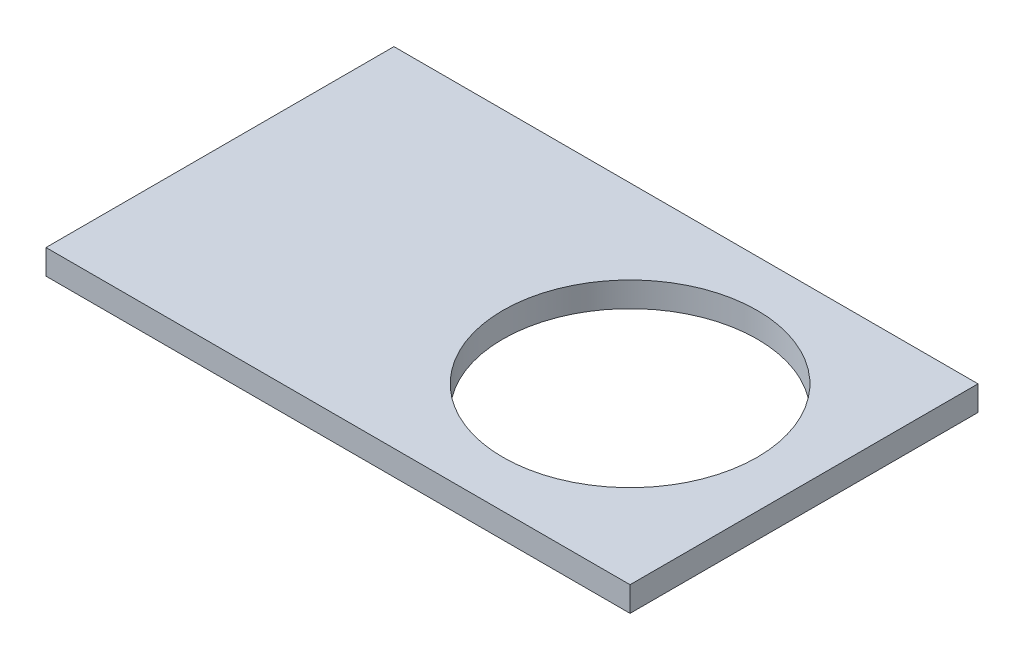
SolidWorks part; units mm, degrees
ref_plane "Front Plane" through (0, 0, 0) normal (0, 0, 1) x (1, 0, 0)
ref_plane "Top Plane" through (0, 0, 0) normal (0, 1, 0) x (1, 0, 0)
ref_plane "Right Plane" through (0, 0, 0) normal (1, 0, 0) x (0, 0, -1)
other "Bounding Box"
ref_plane "Default Plane" through (-8.9266, -12.7485, 0) normal (-0.1736, 0.9848, 0) x (0.9848, 0.1736, 0)
sketch "Sketch1" plane through (0, 0, 0) normal (0, 1, 0) x (1, 0, 0)
  line L0 (0, 0) -> (120.65, 0) construction
  line L1 (-120.65, 0) -> (0, 0) construction
  line L3 (-9.525, 190.5) -> (-3.175, 190.5)
  line L4 (-9.525, 190.5) -> (-9.525, 76.2)
  line L5 (-9.525, 76.2) -> (-3.175, 76.2)
  line L6 (-3.175, 190.5) -> (-3.175, 76.2)
  line L7 (-9.525, 190.5) -> (-3.175, 76.2) construction
  line L8 (-9.525, 76.2) -> (-3.175, 190.5) construction
  line L14 (-165.1, -69.85) -> (165.1, -69.85)
  line L18 (-120.65, 0) -> (-70.8639, 20.8482) construction
  line L19 (70.8639, 20.8482) -> (120.65, 0) construction
  line L20 (-15.875, 44.45) -> (0, 44.45) construction
  line L21 (-6.35, 133.35) -> (0, 133.35)
  line L29 (0, 0) -> (0, -12.7) construction
  line L30 (-120.65, 0) -> (-135.6092, -44.4247) construction
  line L43 (-135.6092, -44.4247) -> (-70.8639, 20.8482) construction
  line L69 (-165.1, -69.85) -> (-165.1, 44.45)
  line L70 (-165.1, 44.45) -> (165.1, 44.45)
  line L71 (165.1, -69.85) -> (165.1, 44.45)
  line L72 (-165.1, -69.85) -> (165.1, 44.45) construction
  line L73 (-165.1, 44.45) -> (165.1, -69.85) construction
  line L78 (0, 133.35) -> (0, -19.05)
  line L79 (0, -19.05) -> (0, -171.45) construction
  line L80 (-9.525, -228.6) -> (-3.175, -228.6) construction
  line L81 (-9.525, -228.6) -> (-9.525, -114.3) construction
  line L82 (-9.525, -114.3) -> (-3.175, -114.3) construction
  line L83 (-3.175, -228.6) -> (-3.175, -114.3) construction
  line L84 (-9.525, -228.6) -> (-3.175, -114.3) construction
  line L85 (-9.525, -114.3) -> (-3.175, -228.6) construction
  line L86 (0, -171.45) -> (-6.35, -171.45) construction
  line L87 (-22.225, -69.85) -> (-15.875, -69.85)
  line L88 (-22.225, -69.85) -> (-22.225, 44.45)
  line L89 (-22.225, 44.45) -> (-15.875, 44.45)
  line L90 (-15.875, -69.85) -> (-15.875, 44.45)
  line L91 (22.225, -69.85) -> (15.875, -69.85)
  line L92 (22.225, -69.85) -> (22.225, 44.45)
  line L93 (22.225, 44.45) -> (15.875, 44.45)
  line L94 (15.875, -69.85) -> (15.875, 44.45)
  line L95 (0, 44.45) -> (15.875, 44.45) construction
  circle A0 centre (-120.65, 0) radius 32.5
  circle A1 centre (-120.65, 0) radius 25
  circle A2 centre (120.65, 0) radius 32.5
  circle A3 centre (120.65, 0) radius 25
  circle A4 centre (-70.8639, 20.8482) radius 17.5006
  circle A5 centre (70.8639, 20.8482) radius 17.5006
  point P8 (-6.35, 133.35)
  point P15 (0, 0)
  point P21 (120.65, 32.5)
  point P25 (70.8639, 38.3488)
  point P27 (-99.7073, -49.7464)
  point P28 (-135.6092, -44.4247)
  point P29 (70.8639, 3.3476)
  point P31 (70.8639, 20.8482)
  point P32 (-6.35, -171.45)
  point P62 (153.15, 0)
  dimension "D1" = 50
  dimension "D2" = 65
  dimension "D8" = 35.0012
  dimension "D11" = 152.4
  dimension "D12" = 19.05
  dimension "D3" = 114.3
  dimension "D4" = 6.35
  dimension "D5" = 241.3
  dimension "D6" = 44.45
  dimension "D7" = 44.45
  dimension "D9" = 114.3
  dimension "D10" = 9.525
  dimension "D13" = 6.35
  dimension "D14" = 31.75
  dimension "D26" = 53.975
sketch "Sketch2" plane through (0, 0, 0) normal (1, 0, 0) x (0, 0, -1)
  line L0 (0, 25.4) -> (0, 45.325) construction
  line L1 (-32.5, 50.325) -> (32.5, 50.325)
  line L2 (-32.5, 50.325) -> (-32.5, 40.325)
  line L3 (-32.5, 40.325) -> (32.5, 40.325)
  line L4 (32.5, 50.325) -> (32.5, 40.325)
  line L5 (-32.5, 50.325) -> (32.5, 40.325) construction
  line L6 (-32.5, 40.325) -> (32.5, 50.325) construction
  line L7 (-32.5, 82.55) -> (32.5, 82.55)
  line L8 (-32.5, 82.55) -> (-32.5, 72.55)
  line L9 (-32.5, 72.55) -> (32.5, 72.55)
  line L10 (32.5, 82.55) -> (32.5, 72.55)
  line L11 (-32.5, 82.55) -> (32.5, 72.55) construction
  line L12 (-32.5, 72.55) -> (32.5, 82.55) construction
  line L13 (-25.8191, 0) -> (33.9817, 0) construction
  line L14 (-19.05, 63.5) -> (-171.45, 63.5)
  line L15 (-69.85, 82.55) -> (44.45, 82.55)
  line L16 (-69.85, 82.55) -> (-69.85, 40.325)
  line L17 (-69.85, 40.325) -> (44.45, 40.325)
  line L18 (44.45, 82.55) -> (44.45, 40.325)
  line L21 (133.35, 0) -> (-19.05, 0) construction
  line L22 (-69.85, 76.2) -> (44.45, 76.2)
  line L23 (-69.85, 46.675) -> (44.45, 46.675)
  line L24 (-19.05, 35.3831) -> (-60.5432, 35.3831) construction
  line L25 (-19.05, 35.3831) -> (-19.05, 63.5) construction
  line L26 (-19.05, 63.5) -> (-60.5432, 35.3831) construction
  line L40 (3.3476, 31.6992) -> (38.3488, 31.6992)
  line L41 (3.3476, 31.6992) -> (3.3476, 76.2)
  line L42 (3.3476, 76.2) -> (38.3488, 76.2)
  line L43 (38.3488, 31.6992) -> (38.3488, 76.2)
  line L44 (3.3476, 31.6992) -> (38.3488, 76.2) construction
  line L45 (3.3476, 76.2) -> (38.3488, 31.6992) construction
  line L46 (-44.45, 82.55) -> (-44.45, 40.325)
  line L47 (-44.45, 61.4375) -> (0, 61.4375) construction
  line L48 (0, 61.4375) -> (44.45, 61.4375) construction
  circle A0 centre (0, 25.4) radius 25.4
  circle A1 centre (-60.5432, 35.3831) radius 18
  circle A2 centre (-19.05, 35.3831) radius 17.78
  circle A3 centre (-171.45, 63.5) radius 57.15
  circle A4 centre (-19.05, 63.5) radius 4.7625
  point P2 (0, 45.325)
  point P8 (0, 77.55)
  point P16 (20.8482, 55.5271)
  point P32 (20.8482, 53.9496)
  point P34 (-228.6, 63.5)
  point P35 (-16.6311, 51.8439)
  point P36 (-69.85, 83.0437)
  point P37 (-69.85, 79.8849)
  point P38 (-69.85, 78.1447)
  point P39 (38.3488, 134.1746)
  point P53 (-23.7979, -7.9114)
  point P55 (-84.9507, -10.5296)
  point P57 (27.558, -29.0148)
  point P58 (-69.85, 84.5719)
  point P59 (0, 0)
  point P60 (-19.05, 35.3831)
  point P61 (-58.9456, 33.6356)
  point P62 (-60.5432, 35.3831)
  dimension "D1" = 50.8
  dimension "D8" = 36
  dimension "D2" = 35.56
  dimension "D11" = 9.525
  dimension "D3" = 10
  dimension "D4" = 82.55
  dimension "D5" = 22.225
  dimension "D6" = 6.35
  dimension "D7" = 6.35
  dimension "D9" = 63.5
  dimension "D10" = 44.5008
ref_plane "Plane1" through (0, 76.2, 0) normal (0, 1, 0) x (1, 0, 0)
sketch "Sketch3" plane through (0, 76.2, 0) normal (0, 1, 0) x (1, 0, 0)
  line L0 (165.1, -69.85) -> (165.1, 44.45) construction
  line L1 (15.875, 44.45) -> (165.1, 44.45)
  line L2 (15.875, 44.45) -> (15.875, -44.45)
  line L3 (15.875, -44.45) -> (165.1, -44.45)
  line L4 (165.1, 44.45) -> (165.1, -44.45)
  circle A0 centre (120.65, 0) radius 32.5 construction
  circle A1 centre (120.65, 0) radius 32.5
extrude "Boss-Extrude1" add sketch "Sketch3" along normal up to vertex (6.35 mm away) up to point (0, 82.55, -44.45)
ref_plane "Plane2" through (0, 46.675, 0) normal (0, -1, 0) x (-1, 0, 0)
sketch "Sketch4" plane through (0, 46.675, 0) normal (0, -1, 0) x (-1, 0, 0)
  line L4 (-15.875, -44.45) -> (-15.875, 44.45)
  line L5 (-15.875, 44.45) -> (-165.1, 44.45)
  line L6 (-165.1, 44.45) -> (-165.1, -44.45)
  line L7 (-165.1, -44.45) -> (-15.875, -44.45)
  line L8 (-15.875, -44.45) -> (-15.875, 44.45)
  line L9 (-15.875, 44.45) -> (-165.1, 44.45)
  line L10 (-165.1, 44.45) -> (-165.1, -44.45)
  line L11 (-165.1, -44.45) -> (-15.875, -44.45)
  circle A0 centre (-120.65, 0) radius 32.5 construction
  circle A1 centre (-120.65, 0) radius 32.5
  dimension "D1" = 0
